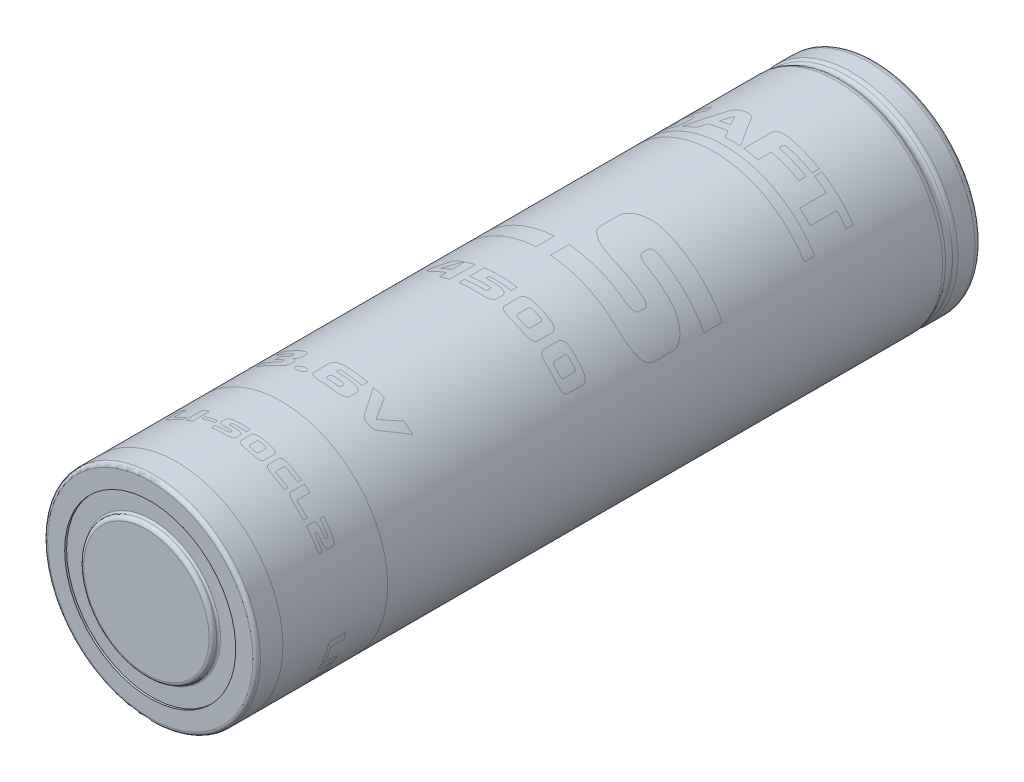
SolidWorks part; units mm, degrees
ref_plane "Front Plane" through (0, 0, 0) normal (0, 0, 1) x (1, 0, 0)
ref_plane "Top Plane" through (0, 0, 0) normal (0, 1, 0) x (1, 0, 0)
ref_plane "Right Plane" through (0, 0, 0) normal (1, 0, 0) x (0, 0, -1)
sketch "Sketch1" plane through (0, 0, 0) normal (1, 0, 0) x (0, 0, -1)
  line L0 (0.381, 4.572) -> (0.381, 5.715)
  line L1 (0.381, 5.715) -> (0.254, 5.715)
  line L2 (0.254, 5.715) -> (0.254, 6.858)
  line L3 (0.508, 7.112) -> (46.101, 7.112)
  line L4 (47.117, 7.112) -> (48.26, 7.112)
  line L5 (48.768, 6.604) -> (48.768, 4.826)
  line L6 (48.768, 4.826) -> (48.641, 4.826)
  line L7 (48.641, 4.826) -> (48.641, 2.413)
  line L8 (48.641, 2.413) -> (49.911, 2.413)
  line L9 (50.292, 2.032) -> (50.292, 0)
  line L10 (50.292, 0) -> (9.3874, 0)
  line L11 (46.609, 6.9596) -> (46.609, 7.3745) construction
  line L12 (0, 4.191) -> (0, 0)
  line L13 (9.3874, 0) -> (3.7242, 0)
  line L14 (3.7242, 0) -> (0, 0)
  arc A0 (0.254, 6.858) -> (0.508, 7.112) centre (0.508, 6.858) cw
  arc A1 (46.101, 7.112) -> (46.3806, 7.0281) centre (46.101, 6.604) cw
  arc A2 (46.3806, 7.0281) -> (46.8374, 7.0281) centre (46.609, 7.3745) ccw
  arc A3 (46.8374, 7.0281) -> (47.117, 7.112) centre (47.117, 6.604) cw
  arc A4 (48.26, 7.112) -> (48.768, 6.604) centre (48.26, 6.604) cw
  arc A5 (49.911, 2.413) -> (50.292, 2.032) centre (49.911, 2.032) cw
  arc A6 (0.381, 4.572) -> (0.254, 4.445) centre (0.254, 4.572) cw
  arc A7 (0.254, 4.445) -> (0, 4.191) centre (0.254, 4.191) ccw
  dimension "D1" = 0.254
  dimension "D3" = 0.1524
  dimension "D4" = 0.508
  dimension "D8" = 0.508
  dimension "D12" = 0.381
  dimension "D18" = 0.127
  dimension "D19" = 0.254
  dimension "D2" = 1.016
  dimension "D5" = 0.127
  dimension "D6" = 5.715
  dimension "D9" = 0.127
  dimension "D13" = 48.768
  dimension "D14" = 50.292
  dimension "D15" = 2.159
  dimension "D16" = 0.254
revolve "Revolve1" add sketch "Sketch1" angle 360 about L10
ref_plane "Plano1" through (0, 10, 0) normal (0, 1, 0) x (1, 0, 0)
sketch "Esboço1" plane through (0, 10, 0) normal (0, 1, 0) x (1, 0, 0)
  line L0 (-11.3158, 39.1307) -> (11.3158, 39.1307) construction
  line L1 (-12.7566, 26.4784) -> (12.7566, 26.4784) construction
  line L2 (-7.2282, 38.6178) -> (7.2282, 38.6178)
  line L3 (-7.2282, 38.6178) -> (-7.2282, 37.9201)
  line L4 (-7.2282, 37.9201) -> (7.2282, 37.9201)
  line L5 (7.2282, 38.6178) -> (7.2282, 37.9201)
  line L6 (-7.2282, 38.6178) -> (7.2282, 37.9201) construction
  line L7 (-7.2282, 37.9201) -> (7.2282, 38.6178) construction
  line L8 (-19.8916, 21.879) -> (20.1084, 21.879) construction
  line L10 (-8.4897, 9.0124) -> (25.9591, 9.0124)
  line L11 (-8.4897, 9.0124) -> (-8.4897, 2.0124)
  line L12 (-8.4897, 2.0124) -> (25.9591, 2.0124)
  line L13 (25.9591, 9.0124) -> (25.9591, 2.0124)
  text T0 "SaFT" font "xscale" height in points 8
  text T1 "LS" font "xscale" height in points 20
  text T2 "14500\r\n\r\n3.6V\r\n" font "xscale" height in points 6
  point P3 (0, 39.1307)
  point P4 (0, 38.269)
  point P12 (0, 26.4784)
  point P16 (-3.443, 21.879)
  dimension "D1" = 40
  dimension "D2" = 7
wrap "Envolver1" sketch "Esboço1" wrap type scribe source sketch "Esboço1"
sketch "Esboço2" plane through (0, 10, 0) normal (0, 1, 0) x (1, 0, 0)
  line L1 (-5.3922, 38.6966) -> (5.3922, 38.6966)
  line L2 (-5.3922, 38.6966) -> (-5.3922, 37.3935)
  line L3 (-5.3922, 37.3935) -> (5.3922, 37.3935)
  line L4 (5.3922, 38.6966) -> (5.3922, 37.3935)
  line L5 (-5.3922, 38.6966) -> (5.3922, 37.3935) construction
  line L6 (-5.3922, 37.3935) -> (5.3922, 38.6966) construction
  point P0 (0, 38.045)
ref_plane "Plano2" through (0, 20, 0) normal (0, 1, 0) x (1, 0, 0)
sketch "Esboço3" plane through (0, 20, 0) normal (0, 1, 0) x (1, 0, 0)
  line L0 (-10.8943, 5.2153) -> (30.1104, 5.2153) construction
  text T0 "li-socl2     lithium" font "xscale" height in points 4
wrap "Envolver2" sketch "Esboço3" wrap type scribe source sketch "Esboço3" face at (0.8306, 0.2963, -5.5124)
ref_plane "Plano3" through (-10, 0, 0) normal (1, 0, 0) x (0, 0, -1)
sketch "Esboço4" plane through (-10, 0, 0) normal (1, 0, 0) x (0, 0, -1)
  line L0 (45.3587, -0.726) -> (1.1461, -0.726) construction
  text T0 "+            -" font "xscale" height 3.175
wrap "Envolver3" sketch "Esboço4" wrap type scribe source sketch "Esboço4" face at (0.8306, 0.2963, -5.5124)
